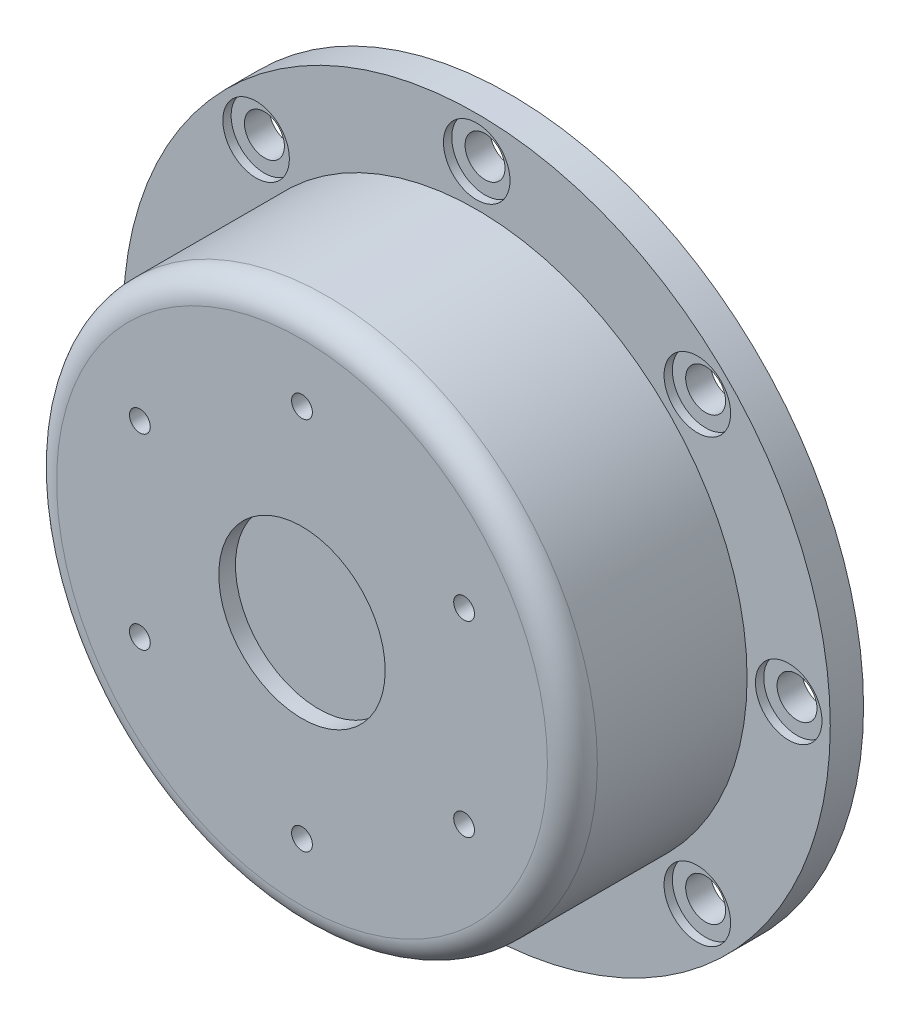
SolidWorks part; units mm, degrees
ref_plane "前视基准面" through (0, 0, 0) normal (0, 0, 1) x (1, 0, 0)
ref_plane "上视基准面" through (0, 0, 0) normal (0, 1, 0) x (1, 0, 0)
ref_plane "右视基准面" through (0, 0, 0) normal (1, 0, 0) x (0, 0, -1)
sketch "草图1" plane through (0, 0, 0) normal (0, 0, 1) x (1, 0, 0)
  circle A0 centre (0, 0) radius 42.5
  dimension "D1" = 85
extrude "凸台-拉伸1" add sketch "草图1" along normal blind 25
sketch "草图2" plane through (0, 0, 25) normal (0, 0, 1) x (1, 0, 0)
  circle A0 centre (0, 0) radius 32.5
  dimension "D1" = 65
extrude "切除-拉伸1" cut sketch "草图2" against normal offset from surface (21 mm away) 4 flip side to cut up to face at (42.5, 0, 0)
hole_wizard "打孔尺寸(%根据)内六角圆柱头螺钉的类型1" positions "草图4" profile "草图3" counterbore size "M4" standard "GB"
sketch "草图4" plane through (0, 0, 4) normal (0, 0, 1) x (1, 0, 0)
  line L0 (0, 0) -> (0, 45.1095) construction
  circle A0 centre (0, 0) radius 37.5 construction
  point P0 (0, 37.5)
  dimension "D1" = 75
sketch "草图3" plane through (0, 37.5, 4) normal (1, 0, 0) x (0, -1, 0)
  line L0 (0, 0) -> (0, 7.9421)
  line L1 (0, 7.9421) -> (2.4, 6.5)
  line L2 (2.4, 6.5) -> (2.4, 1)
  line L3 (2.4, 1) -> (4, 1)
  line L4 (4, 1) -> (4, 0)
  line L5 (4, 0) -> (0, 0)
  line L10 (0, 7.9421) -> (-2.4, 6.5) construction
  line L11 (0, -6.35) -> (0, 107.95) construction
  dimension "孔直径" = 4.8
  dimension "孔深度" = 6.5
  dimension "柱形沉头孔直径" = 8
  dimension "柱形沉头孔深度" = 1
  dimension "导头角度" = 118
ref_axis "基准轴1" through (0, 0, 4) along (0, 0, -1)
pattern_circular "阵列(圆周)1" count 8 over 360 about axis through (0, 0, 4) along (0, 0, -1) of "打孔尺寸(%根据)内六角圆柱头螺钉的类型1"
sketch "草图5" plane through (0, 0, 25) normal (0, 0, 1) x (1, 0, 0)
  circle A0 centre (0, 0) radius 10
  dimension "D1" = 20
extrude "切除-拉伸2" cut sketch "草图5" against normal blind 2
hole_wizard "M3 螺纹孔1" positions "草图7" profile "草图6" tap size "M3" standard "GB"
sketch "草图7" plane through (0, 0, 25) normal (0, 0, 1) x (1, 0, 0)
  line L0 (0, 0) -> (0, 44.523) construction
  circle A0 centre (0, 0) radius 22.5 construction
  point P0 (0, 22.5)
  dimension "D1" = 45
sketch "草图6" plane through (0, 22.5, 25) normal (1, 0, 0) x (0, -1, 0)
  line L0 (0, 0) -> (0, 7.2511)
  line L1 (0, 7.2511) -> (1.25, 6.5)
  line L2 (1.25, 6.5) -> (1.25, 0)
  line L5 (1.25, 0) -> (0, 0)
  line L10 (0, 7.2511) -> (-1.25, 6.5) construction
  line L11 (0, -6.35) -> (0, 107.95) construction
  dimension "螺纹孔钻头直径" = 2.5
  dimension "螺纹孔钻头深度" = 6.5
  dimension "导头角度" = 118
cosmetic thread "孔螺蚊线1" parameters "D1"=5, "D2"=3
pattern_circular "阵列(圆周)2" count 6 over 360 about axis through (0, 0, 4) along (0, 0, -1) of "M3 螺纹孔1"
fillet "圆角1" radius 3 1 edges at (32.5, 0, 25)
